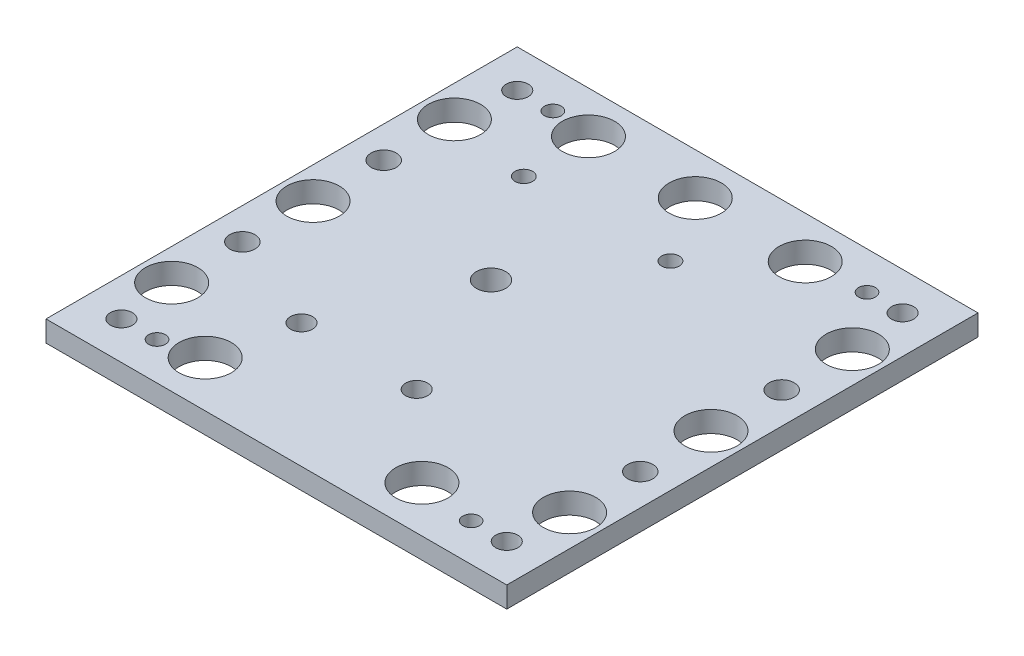
SolidWorks part; units mm, degrees
material "K110"
ref_plane "Front Plane" through (0, 0, 0) normal (0, 0, 1) x (1, 0, 0)
ref_plane "Top Plane" through (0, 0, 0) normal (0, 1, 0) x (1, 0, 0)
ref_plane "Right Plane" through (0, 0, 0) normal (1, 0, 0) x (0, 0, -1)
sketch "Sketch1" plane through (0, 0, 0) normal (0, 1, 0) x (1, 0, 0)
  line L1 (-110, -112.5) -> (110, -112.5)
  line L2 (-110, -112.5) -> (-110, 112.5)
  line L3 (-110, 112.5) -> (110, 112.5)
  line L4 (110, -112.5) -> (110, 112.5)
  line L5 (-110, -112.5) -> (110, 112.5) construction
  line L6 (-110, 112.5) -> (110, -112.5) construction
  point P0 (0, 0)
  dimension "D1" = 220
  dimension "D2" = 225
extrude "Boss-Extrude1" add sketch "Sketch1" along normal blind 10
sketch "Sketch3" plane through (0, 0, 0) normal (0, -1, 0) x (1, 0, 0)
  circle A0 centre (-19.87, -9.86) radius 7 construction
  circle A1 centre (-19.87, -9.86) radius 7
extrude "Cut-Extrude2" cut sketch "Sketch3" against normal up to next
hole_wizard "Ø8.0mm Dowel Hole1" positions "Sketch7" profile "Sketch5" hole size "Ø8.0" standard "ISO" end condition through all
sketch "Sketch7" plane through (0, 10, 0) normal (0, 1, 0) x (1, 0, 0)
  point P0 (75, -94.5)
  point P3 (-75, -94.5)
  point P6 (75, 94.5)
  point P10 (-75, 94.5)
sketch "Sketch5" plane through (75, 10, 94.5) normal (1, 0, 0) x (0, 0, 1)
  line L0 (0, 0) -> (0, 10)
  line L1 (0, 10) -> (4, 10)
  line L2 (4, 10) -> (4, 0)
  line L5 (4, 0) -> (0, 0)
  line L11 (0, -6.35) -> (0, 107.95) construction
  dimension "Thru Hole Dia." = 8
  dimension "Thru Hole Depth" = 10
hole_wizard "M10 Clearance Hole1" positions "Sketch10" profile "Sketch9" hole size "M10" standard "ISO" end condition through all
sketch "Sketch10" plane through (0, 10, 0) normal (0, 1, 0) x (1, 0, 0)
  point P0 (92, -94.5)
  point P3 (92, 94.5)
  point P6 (-92, 94.5)
  point P9 (-92, -94.5)
sketch "Sketch9" plane through (92, 10, 94.5) normal (1, 0, 0) x (0, 0, 1)
  line L0 (0, 0) -> (0, 10)
  line L1 (0, 10) -> (5.25, 10)
  line L2 (5.25, 10) -> (5.25, 0)
  line L5 (5.25, 0) -> (0, 0)
  line L11 (0, -6.35) -> (0, 107.95) construction
  dimension "Thru Hole Dia." = 10.5
  dimension "Thru Hole Depth" = 10
hole_wizard "M10 Clearance Hole2" positions "Sketch13" profile "Sketch12" hole size "M10" standard "ISO" end condition through all
sketch "Sketch13" plane through (0, 10, 0) normal (0, 1, 0) x (1, 0, 0)
  point P0 (7.63, -53.14)
  point P3 (-47.37, -53.14)
sketch "Sketch12" plane through (7.63, 10, 53.14) normal (1, 0, 0) x (0, 0, 1)
  line L0 (0, 0) -> (0, 10)
  line L1 (0, 10) -> (5.25, 10)
  line L2 (5.25, 10) -> (5.25, 0)
  line L5 (5.25, 0) -> (0, 0)
  line L11 (0, -6.35) -> (0, 107.95) construction
  dimension "Thru Hole Dia." = 10.5
  dimension "Thru Hole Depth" = 10
hole_wizard "M8 Clearance Hole1" positions "Sketch16" profile "Sketch15" hole size "M8" standard "ISO" end condition through all
sketch "Sketch16" plane through (0, 10, 0) normal (0, 1, 0) x (1, 0, 0)
  point P0 (15.13, 60.5)
  point P3 (-54.87, 60.5)
sketch "Sketch15" plane through (15.13, 10, -60.5) normal (1, 0, 0) x (0, 0, 1)
  line L0 (0, 0) -> (0, 10)
  line L1 (0, 10) -> (4.2, 10)
  line L2 (4.2, 10) -> (4.2, 0)
  line L5 (4.2, 0) -> (0, 0)
  line L11 (0, -6.35) -> (0, 107.95) construction
  dimension "Thru Hole Dia." = 8.4
  dimension "Thru Hole Depth" = 10
sketch "Sketch17" plane through (0, 10, 0) normal (0, 1, 0) x (1, 0, 0)
  circle A0 centre (-95, -67.5) radius 12.5 construction
  circle A1 centre (-95, 0) radius 12.5 construction
  circle A2 centre (-95, 67.5) radius 12.5 construction
  circle A3 centre (-56, -90.5) radius 12.5 construction
  circle A4 centre (47.5, -90.5) radius 12.5 construction
  circle A5 centre (95, -67.5) radius 12.5 construction
  circle A6 centre (95, 0) radius 12.5 construction
  circle A7 centre (95, 67.5) radius 12.5 construction
  circle A8 centre (47.5, 92.5) radius 12.5 construction
  circle A9 centre (-5, 92.5) radius 12.5 construction
  circle A10 centre (-56, 92.5) radius 12.5 construction
  circle A11 centre (-95, -67.5) radius 12.5
  circle A12 centre (-95, 0) radius 12.5
  circle A13 centre (-95, 67.5) radius 12.5
  circle A14 centre (-56, -90.5) radius 12.5
  circle A15 centre (47.5, -90.5) radius 12.5
  circle A16 centre (95, -67.5) radius 12.5
  circle A17 centre (95, 0) radius 12.5
  circle A18 centre (95, 67.5) radius 12.5
  circle A19 centre (47.5, 92.5) radius 12.5
  circle A20 centre (-5, 92.5) radius 12.5
  circle A21 centre (-56, 92.5) radius 12.5
extrude "Cut-Extrude3" cut sketch "Sketch17" against normal up to next
hole_wizard "Ø12.0 (12) Diameter Hole1" positions "Sketch20" profile "Sketch19" hole size "Ø12.0" standard "ISO" end condition through all
sketch "Sketch20" plane through (0, 10, 0) normal (0, 1, 0) x (1, 0, 0)
  line L0 (-95, -67.5) -> (-95, 0) construction
  line L1 (-95, 0) -> (-95, 67.5) construction
  line L3 (95, -67.5) -> (95, 0) construction
  line L4 (95, 0) -> (95, 67.5) construction
  point P19 (-95, -33.75)
  point P21 (-95, 33.75)
  point P23 (95, 33.75)
  point P25 (95, -33.75)
sketch "Sketch19" plane through (95, 10, 33.75) normal (1, 0, 0) x (0, 0, 1)
  line L0 (0, 0) -> (0, 10)
  line L1 (0, 10) -> (6, 10)
  line L2 (6, 10) -> (6, 0)
  line L5 (6, 0) -> (0, 0)
  line L11 (0, -6.35) -> (0, 107.95) construction
  dimension "Thru Hole Dia." = 12
  dimension "Thru Hole Depth" = 10
